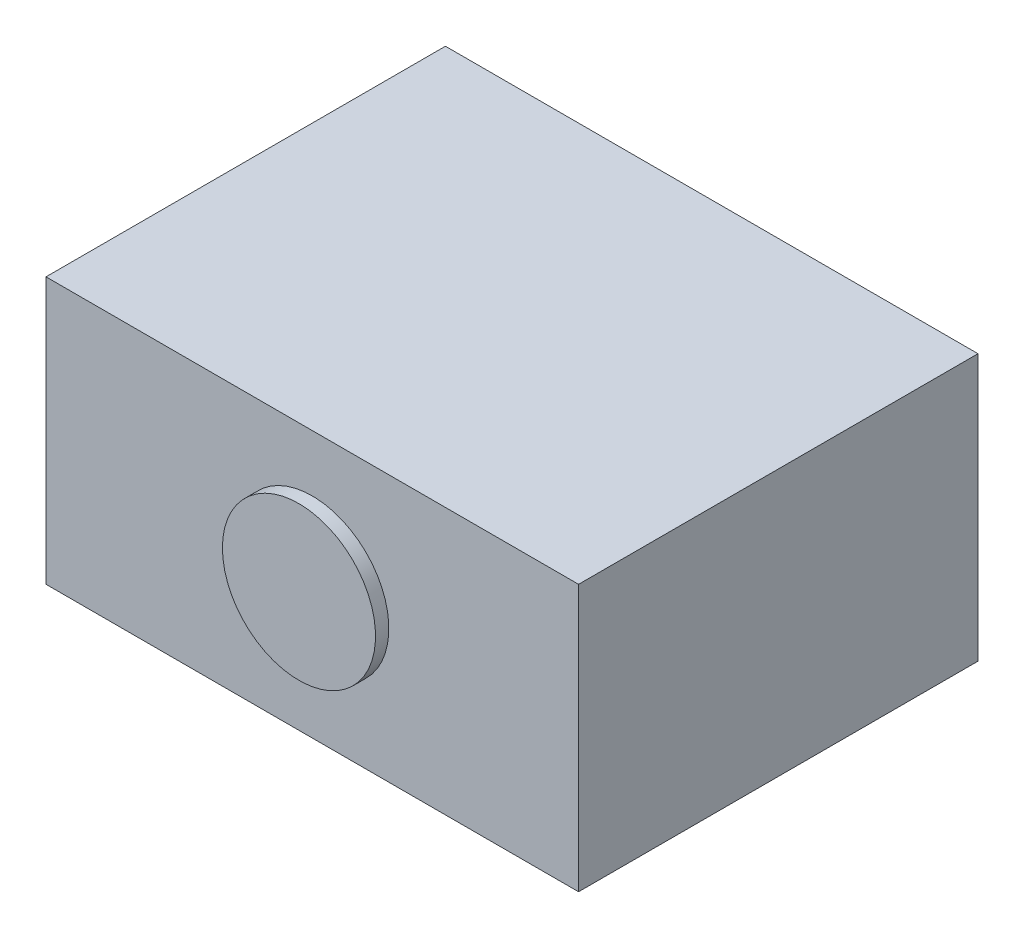
SolidWorks part; units mm, degrees
ref_plane "Front Plane" through (0, 0, 0) normal (0, 0, 1) x (1, 0, 0)
ref_plane "Top Plane" through (0, 0, 0) normal (0, 1, 0) x (1, 0, 0)
ref_plane "Right Plane" through (0, 0, 0) normal (1, 0, 0) x (0, 0, -1)
sketch "Sketch1" plane through (0, 0, 0) normal (0, 0, 1) x (1, 0, 0)
  line L1 (-200, -100) -> (200, -100)
  line L2 (-200, -100) -> (-200, 100)
  line L3 (-200, 100) -> (200, 100)
  line L4 (200, -100) -> (200, 100)
  line L5 (-200, -100) -> (200, 100) construction
  line L6 (-200, 100) -> (200, -100) construction
  point P0 (0, 0)
  dimension "D1" = 400
  dimension "D2" = 200
extrude "Boss-Extrude1" add sketch "Sketch1" along normal blind 150 and the other way blind 150
sketch "Sketch2" plane through (0, 0, 0) normal (0, 0, -1) x (-1, 0, 0)
  circle A0 centre (0, 0) radius 57.5
  dimension "D1" = 115
extrude "Boss-Extrude2" add sketch "Sketch2" along normal blind 160 and the other way blind 160
